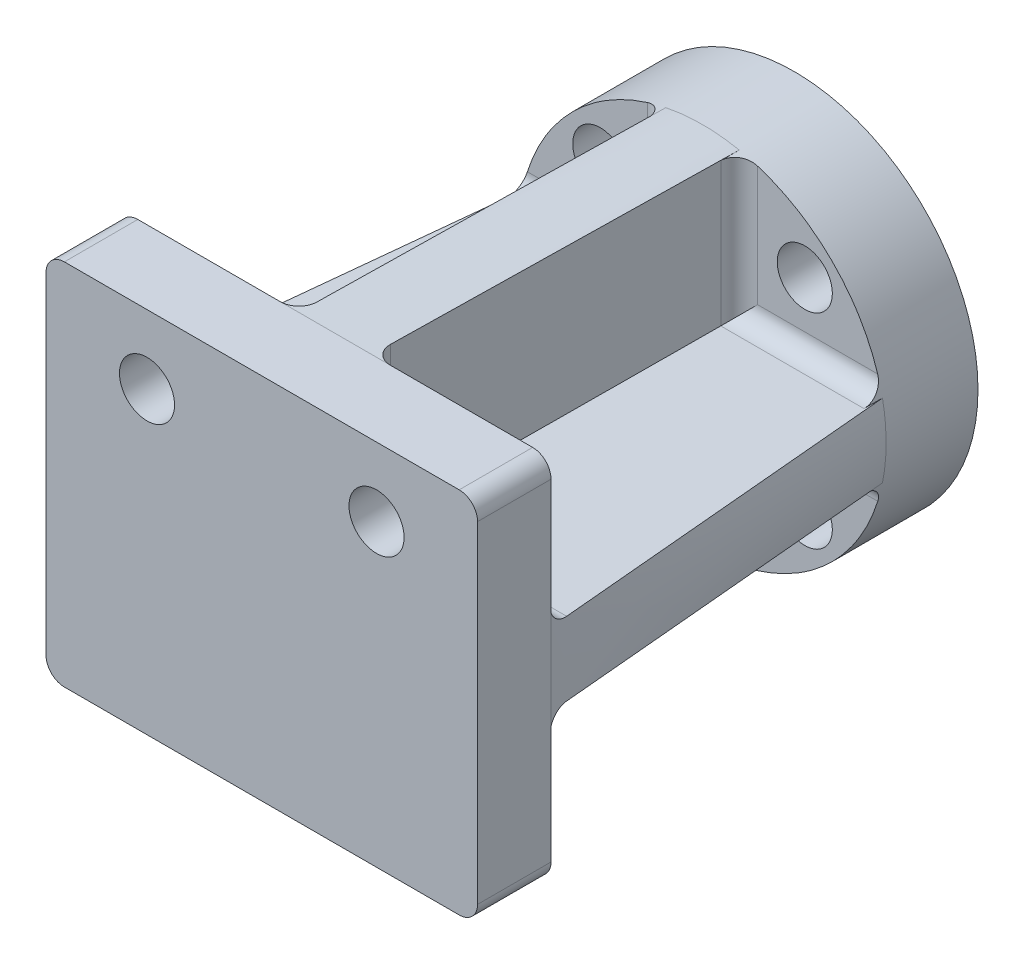
SolidWorks part; units mm, degrees
material "ABS"
ref_plane "Front Plane" through (0, 0, 0) normal (0, 0, 1) x (1, 0, 0)
ref_plane "Top Plane" through (0, 0, 0) normal (0, 1, 0) x (1, 0, 0)
ref_plane "Right Plane" through (0, 0, 0) normal (1, 0, 0) x (0, 0, -1)
sketch "Sketch1" plane through (0, 0, 0) normal (0, 0, 1) x (1, 0, 0)
  line L0 (-16.2892, 16.2892) -> (11.1062, -11.1062) construction
  line L1 (-22.1963, 0) -> (27.7221, 0) construction
  circle A0 centre (0, 0) radius 20
  circle A2 centre (-11.1369, 11.1369) radius 3
  circle A3 centre (11.1369, 11.1369) radius 3
  circle A4 centre (11.1369, -11.1369) radius 3
  circle A5 centre (-11.1369, -11.1369) radius 3
  circle A6 centre (0, 0) radius 15.75 construction
  point P17 (0, 0)
  dimension "D2" = 40
  dimension "D3" = 6
  dimension "D4" = 31.5
  dimension "D5" = 45
  dimension "D1" = 4
extrude "Boss-Extrude1" add sketch "Sketch1" along normal blind 10
ref_plane "Plane1" through (0, 0, 50) normal (0, 0, 1) x (1, 0, 0)
sketch "Sketch4" plane through (0, 0, 50) normal (0, 0, 1) x (1, 0, 0)
  line L0 (-23.5, 12.8) -> (23.5, 12.8) construction
  line L1 (-23.5, -20.3) -> (23.5, -20.3)
  line L2 (-23.5, -20.3) -> (-23.5, 20.3)
  line L3 (-23.5, 20.3) -> (23.5, 20.3)
  line L4 (23.5, -20.3) -> (23.5, 20.3)
  line L5 (-23.5, -20.3) -> (23.5, 20.3) construction
  line L6 (-23.5, 20.3) -> (23.5, -20.3) construction
  line L7 (0, 23.7998) -> (0, 0) construction
  circle A0 centre (-12.5, 12.8) radius 3
  circle A1 centre (12.5, 12.8) radius 3
  point P0 (0, 0)
  dimension "D5" = 6
  dimension "D1" = 40.6
  dimension "D2" = 47
  dimension "D3" = 7.5
  dimension "D4" = 25
extrude "Boss-Extrude3" add sketch "Sketch4" along normal blind 8 separate body
sketch "Sketch6" plane through (0, 0, 58) normal (0, 0, 1) x (1, 0, 0)
  line L0 (23.5, -20.3) -> (23.5, 20.3) construction
  line L1 (-23.5, -20.3) -> (23.5, -20.3)
  line L2 (-23.5, -20.3) -> (-23.5, -19.8)
  line L3 (-23.5, -19.8) -> (23.5, -19.8)
  line L4 (23.5, -20.3) -> (23.5, -19.8)
  dimension "D1" = 0.5
extrude "Cut-Extrude1" cut sketch "Sketch6" against normal blind 10
sketch "Sketch7" plane through (0, 0, 50) normal (0, 0, -1) x (-1, 0, 0)
  line L0 (-23.5, 20.3) -> (23.5, 20.3) construction
  line L2 (-4.0032, -19.8) -> (-4.0032, -3.75)
  line L3 (-4.0032, 20.3) -> (3.9968, 20.3)
  line L4 (3.9968, -19.8) -> (3.9968, -3.75)
  line L5 (-3.8983, -19.8) -> (3.9968, 20.3) construction
  line L6 (-4.0032, 20.3) -> (3.9046, -19.8) construction
  line L7 (23.5, 20.3) -> (23.5, -19.8) construction
  line L8 (-23.4016, 4.25) -> (-4.0032, 4.25)
  line L9 (-23.4016, 4.25) -> (-23.4016, -3.75)
  line L10 (-23.4016, -3.75) -> (-4.0032, -3.75)
  line L11 (23.5, 4.25) -> (23.5, -3.75)
  line L12 (-23.4016, 4.25) -> (23.5, -3.75) construction
  line L13 (-23.4016, -3.75) -> (23.5, 4.25) construction
  line L14 (3.9968, 4.25) -> (3.9968, 20.3)
  line L15 (3.9968, 4.25) -> (23.5, 4.25)
  line L16 (-4.0032, 4.25) -> (-4.0032, 20.3)
  line L17 (3.9968, -3.75) -> (23.5, -3.75)
  line L18 (-4.0032, -19.8) -> (3.9968, -19.8)
  line L19 (23.5, -19.8) -> (-23.5, -19.8) construction
  point P0 (0, 0)
  point P8 (0.0492, 0.25)
  dimension "D1" = 8
  dimension "D2" = 8
  dimension "D3" = 19.5032
sketch "Sketch8" plane through (0, 0, 10) normal (0, 0, 1) x (1, 0, 0)
  line L0 (-4, 4) -> (-4, 19.5959)
  line L2 (-4, -19.5959) -> (-4, -4)
  line L4 (4, -19.5959) -> (4, -4)
  line L5 (-4, -19.5959) -> (4, 19.5959) construction
  line L6 (-4, 19.5959) -> (4, -19.5959) construction
  line L7 (-19.5959, -4) -> (-4, -4)
  line L9 (-19.5959, 4) -> (-4, 4)
  line L11 (-19.5959, -4) -> (19.5959, 4) construction
  line L12 (-19.5959, 4) -> (19.5959, -4) construction
  line L13 (4, 4) -> (4, 19.5959)
  line L14 (4, 4) -> (19.5959, 4)
  line L15 (4, -4) -> (19.5959, -4)
  circle A0 centre (0, 0) radius 20 construction
  arc A1 (4, 19.5959) -> (-4, 19.5959) centre (0, 0) ccw
  arc A2 (19.5959, -4) -> (19.5959, 4) centre (0, 0) ccw
  arc A3 (-4, -19.5959) -> (4, -19.5959) centre (0, 0) ccw
  arc A4 (-19.5959, 4) -> (-19.5959, -4) centre (0, 0) ccw
  point P0 (0, 0)
  point P8 (0, 0)
  dimension "D1" = 8
  dimension "D2" = 8
loft "Loft1" add profiles "Sketch7", "Sketch8" connector at (4.0032, 4.25, 50) connector at (4, 4, 10)
fillet "Fillet1" radius 2 4 edges at (-23.5, -19.8, 54) (23.5, -19.8, 54) (23.5, 20.3, 54) (-23.5, 20.3, 54)
combine bodies "Combine1" operation type add bodies to combine 104 105
fillet "Fillet2" radius 2 8 edges
fillet "Fillet3" radius 2 8 edges
